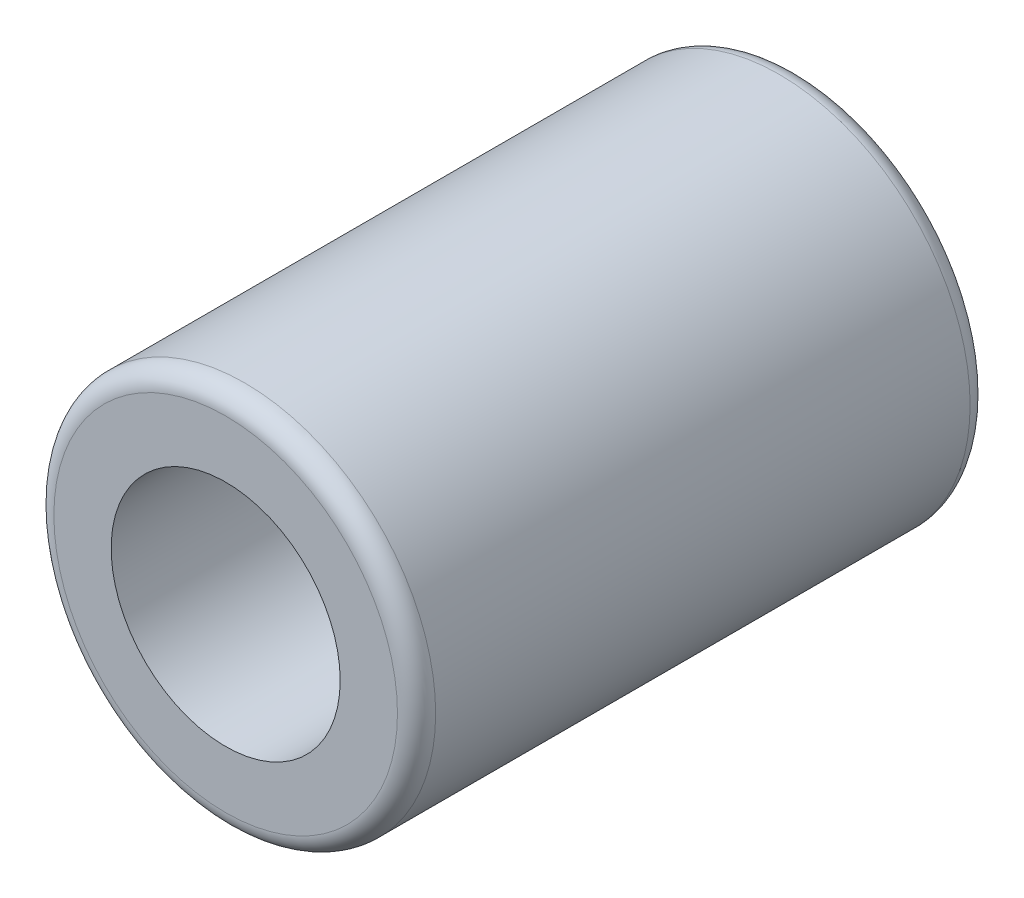
SolidWorks part; units mm, degrees
ref_plane "Front Plane" through (0, 0, 0) normal (0, 0, 1) x (1, 0, 0)
ref_plane "Top Plane" through (0, 0, 0) normal (0, 1, 0) x (1, 0, 0)
ref_plane "Right Plane" through (0, 0, 0) normal (1, 0, 0) x (0, 0, -1)
sketch "Sketch2" plane through (0, 0, 0) normal (0, 0, 1) x (1, 0, 0)
  circle A0 centre (0, 0) radius 5
  circle A1 centre (0, 0) radius 2.5
  dimension "D1" = 10
  dimension "D2" = 5
extrude "Boss-Extrude1" add sketch "Sketch2" along normal blind 15
sketch "Sketch3" plane through (0, 0, 15) normal (0, 0, 1) x (1, 0, 0)
  circle A0 centre (0, 0) radius 3
  dimension "D1" = 6
extrude "Cut-Extrude1" cut sketch "Sketch3" against normal blind 10
sketch "Sketch4" plane through (0, 0, 0) normal (0, 1, 0) x (1, 0, 0)
  circle A0 centre (0, -3.0524) radius 1.5
  circle A1 centre (0, -9.8801) radius 1.5
  point P4 (0, -2.5606)
  point P6 (0, -3.0524)
  point P7 (0, -9.8801)
  dimension "D1" = 3
extrude "Cut-Extrude2" cut sketch "Sketch4" against normal through all
fillet "Fillet1" radius 0.5 2 edges at (5, 0, 15) (5, 0, 0)
